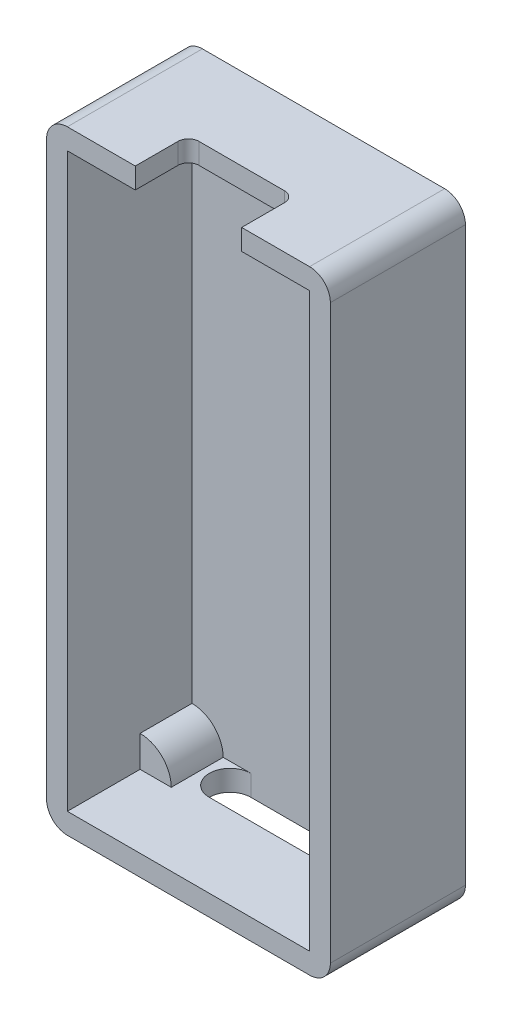
SolidWorks part; units mm, degrees
ref_plane "Front Plane" through (0, 0, 0) normal (0, 0, 1) x (1, 0, 0)
ref_plane "Top Plane" through (0, 0, 0) normal (0, 1, 0) x (1, 0, 0)
ref_plane "Right Plane" through (0, 0, 0) normal (1, 0, 0) x (0, 0, -1)
sketch "Sketch1" plane through (0, 0, 0) normal (0, 0, 1) x (1, 0, 0)
  line L12 (-16.62, -3.82) -> (1.38, -3.82)
  line L13 (1.38, -3.82) -> (1.38, 39.38)
  line L14 (1.38, 39.38) -> (-16.62, 39.38)
  line L15 (-16.62, 39.38) -> (-16.62, -3.82)
  line L16 (-16.62, -3.82) -> (1.38, -3.82) construction
  line L17 (1.38, -3.82) -> (1.38, 39.38) construction
  line L18 (1.38, 39.38) -> (-16.62, 39.38) construction
  line L19 (-16.62, 39.38) -> (-16.62, -3.82) construction
  line L20 (-16.874, 39.634) -> (-16.874, -4.074)
  line L21 (-16.874, -4.074) -> (1.634, -4.074)
  line L22 (1.634, -4.074) -> (1.634, 39.634)
  line L23 (1.634, 39.634) -> (-16.874, 39.634)
  line L24 (-18.4615, 41.2215) -> (-18.4615, -5.6615)
  line L25 (-18.4615, -5.6615) -> (3.2215, -5.6615)
  line L26 (3.2215, -5.6615) -> (3.2215, 41.2215)
  line L27 (3.2215, 41.2215) -> (-18.4615, 41.2215)
  dimension "D1" = 0
  dimension "D2" = 0.254
  dimension "D3" = 1.5875
extrude "Boss-Extrude1" add sketch "Sketch1" against normal blind 3.9688 and the other way blind 5.5562
sketch "Sketch2" plane through (0, 0, -3.9688) normal (0, 0, -1) x (-1, 0, 0)
  line L5 (18.4615, 41.2215) -> (-3.2215, 41.2215)
  line L6 (-3.2215, 41.2215) -> (-3.2215, -5.6615)
  line L7 (-3.2215, -5.6615) -> (18.4615, -5.6615)
  line L8 (18.4615, -5.6615) -> (18.4615, 41.2215)
  line L9 (18.4615, 41.2215) -> (-3.2215, 41.2215)
  line L10 (-3.2215, 41.2215) -> (-3.2215, -5.6615)
  line L11 (-3.2215, -5.6615) -> (18.4615, -5.6615)
  line L12 (18.4615, -5.6615) -> (18.4615, 41.2215)
  dimension "D1" = 0
extrude "Boss-Extrude2" add sketch "Sketch2" along normal blind 0.7937
sketch "Sketch3" plane through (0, 41.2215, 0) normal (0, 1, 0) x (1, 0, 0)
  line L0 (3.2215, -5.5562) -> (-18.4615, -5.5562) construction
  line L1 (-3.556, -5.5563) -> (-11.684, -5.5563)
  line L2 (-3.556, -5.5563) -> (-3.556, -1.4923)
  line L3 (-3.556, -1.4923) -> (-11.684, -1.4923)
  line L4 (-11.684, -5.5563) -> (-11.684, -1.4923)
  line L5 (-18.4615, 4.7625) -> (3.2215, 4.7625) construction
  point P8 (-7.62, 4.7625)
  point P9 (-7.62, -1.4923)
  dimension "D1" = 8.128
  dimension "D2" = 4.064
extrude "Cut-Extrude1" cut sketch "Sketch3" against normal up to next
fillet "Fillet1" radius 0.7937 2 edges at (-11.684, 40.4277, 1.4923) (-3.556, 40.4277, 1.4923)
sketch "Sketch4" plane through (0, 0, -3.9688) normal (0, 0, 1) x (1, 0, 0)
  line L0 (-16.874, -4.074) -> (1.634, -4.074) construction
  line L1 (-16.874, 39.634) -> (-16.874, -4.074) construction
  line L2 (-16.874, -1.6928) -> (-16.874, -4.074)
  line L3 (-16.874, -4.074) -> (-14.4928, -4.074)
  line L4 (-7.62, -4.074) -> (-7.62, 0.6024) construction
  line L5 (-16.874, 17.78) -> (-13.699, 17.78) construction
  line L6 (1.634, -4.074) -> (-0.7472, -4.074)
  line L7 (1.634, -1.6928) -> (1.634, -4.074)
  line L8 (1.634, 37.2527) -> (1.634, 39.634)
  line L9 (1.634, 39.634) -> (-0.7472, 39.634)
  line L10 (-16.874, 39.634) -> (-14.4928, 39.634)
  line L11 (-16.874, 37.2527) -> (-16.874, 39.634)
  arc A0 (-14.4928, -4.074) -> (-16.874, -1.6928) centre (-16.874, -4.074) ccw
  arc A1 (-0.7472, -4.074) -> (1.634, -1.6928) centre (1.634, -4.074) cw
  arc A2 (-0.7472, 39.634) -> (1.634, 37.2527) centre (1.634, 39.634) ccw
  arc A3 (-14.4928, 39.634) -> (-16.874, 37.2527) centre (-16.874, 39.634) cw
  dimension "D1" = 2.3813
extrude "Boss-Extrude3" add sketch "Sketch4" along normal up to surface (3.9688 mm away)
sketch "Sketch5" plane through (0, -5.6615, 0) normal (0, -1, 0) x (1, 0, 0)
  line L0 (-12.3825, -2.3813) -> (-2.8575, -2.3813) construction
  line L1 (-12.3825, -0.7937) -> (-2.8575, -0.7937)
  line L2 (-12.3825, -3.9688) -> (-2.8575, -3.9688)
  line L3 (-14.4927, -3.9688) -> (-16.874, -3.9688) construction
  line L4 (3.2215, -4.7625) -> (-18.4615, -4.7625) construction
  arc A0 (-12.3825, -0.7937) -> (-12.3825, -3.9688) centre (-12.3825, -2.3813) ccw
  arc A1 (-2.8575, -3.9688) -> (-2.8575, -0.7937) centre (-2.8575, -2.3813) ccw
  point P2 (-7.62, -2.3813)
  point P11 (-7.62, -4.7625)
  dimension "D1" = 3.175
  dimension "D2" = 9.525
extrude "Cut-Extrude2" cut sketch "Sketch5" against normal up to next
fillet "Fillet2" radius 1.5875 4 edges at (3.2215, 41.2215, 0.3969) (-18.4615, 41.2215, 0.3969) (-18.4615, -5.6615, 0.3969) (3.2215, -5.6615, 0.3969)
